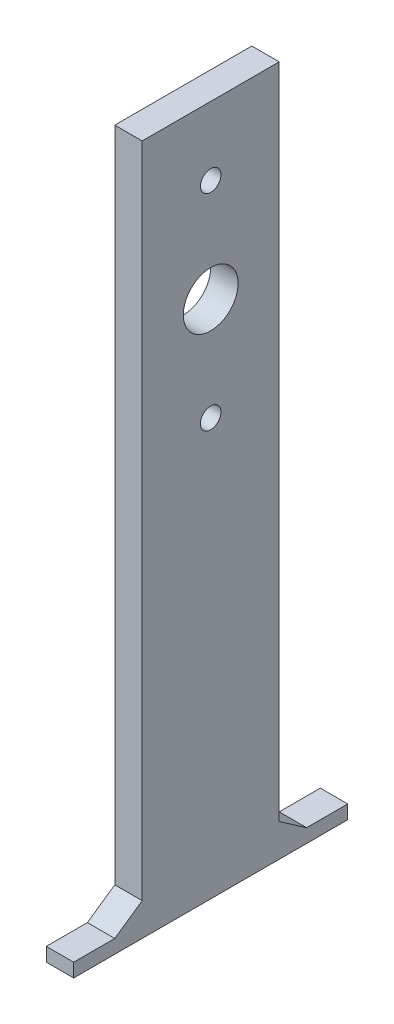
SolidWorks part; units mm, degrees
ref_plane "Front Plane" through (0, 0, 0) normal (0, 0, 1) x (1, 0, 0)
ref_plane "Top Plane" through (0, 0, 0) normal (0, 1, 0) x (1, 0, 0)
ref_plane "Right Plane" through (0, 0, 0) normal (1, 0, 0) x (0, 0, -1)
sketch "Sketch1" plane through (0, 0, 0) normal (0, 1, 0) x (1, 0, 0)
  line L1 (10, 0) -> (10, 50)
  line L2 (0, 0) -> (0, 50)
  line L4 (0, 50) -> (0, 75)
  line L5 (0, 153.69) -> (0, -246.31) construction
  line L6 (0, 75) -> (10, 75)
  line L7 (10, 75) -> (10, 50)
  line L8 (0, 0) -> (0, -25)
  line L9 (0, -25) -> (10, -25)
  line L10 (10, -25) -> (10, 0)
extrude "Boss-Extrude1" add sketch "Sketch1" along normal blind 252
sketch "Sketch3" plane through (0, 0, 0) normal (-1, 0, 0) x (0, 0, 1)
  line L0 (25, 200) -> (25, 5)
  line L2 (-75, 252) -> (25, 252) construction
  line L5 (0, 200) -> (25, 200)
  line L6 (-75, 252) -> (-75, 0) construction
  line L7 (-75, 5) -> (-60, 5)
  line L8 (-60, 5) -> (-50, 11.9378)
  line L9 (-50, 11.9378) -> (-50, 252)
  line L10 (-50, 252) -> (-75, 252)
  line L11 (-75, 252) -> (-75, 5)
  line L12 (0, 11.9378) -> (0, 200)
  line L13 (10, 5) -> (0, 11.9378)
  line L14 (25, 5) -> (10, 5)
extrude "Cut-Extrude2" cut sketch "Sketch3" against normal blind 10
sketch "Sketch4" plane through (10, 0, 0) normal (1, 0, 0) x (0, 0, -1)
  line L0 (0, 200) -> (0, 252)
  line L1 (-25, 252) -> (50, 252) construction
  line L2 (0, 252) -> (-25, 252)
  line L3 (-25, 252) -> (-25, 200)
  line L4 (-25, 200) -> (0, 200)
extrude "Cut-Extrude3" cut sketch "Sketch4" against normal blind 10
sketch "Sketch5" plane through (10, 0, 0) normal (1, 0, 0) x (0, 0, -1)
  line L0 (25, 227) -> (25, 252) construction
  line L1 (0, 252) -> (50, 252) construction
  line L2 (25, 227) -> (25, 189.5) construction
  line L3 (25, 189.5) -> (25, 152) construction
  circle A0 centre (25, 227) radius 3.75
  circle A1 centre (25, 189.5) radius 10
  circle A2 centre (25, 152) radius 3.75
  dimension "D1" = 25
  dimension "D4" = 20
  dimension "D5" = 7.5
  dimension "D6" = 7.5
  dimension "D2" = 37.5
  dimension "D3" = 37.5
extrude "Cut-Extrude5" cut sketch "Sketch5" against normal through all
